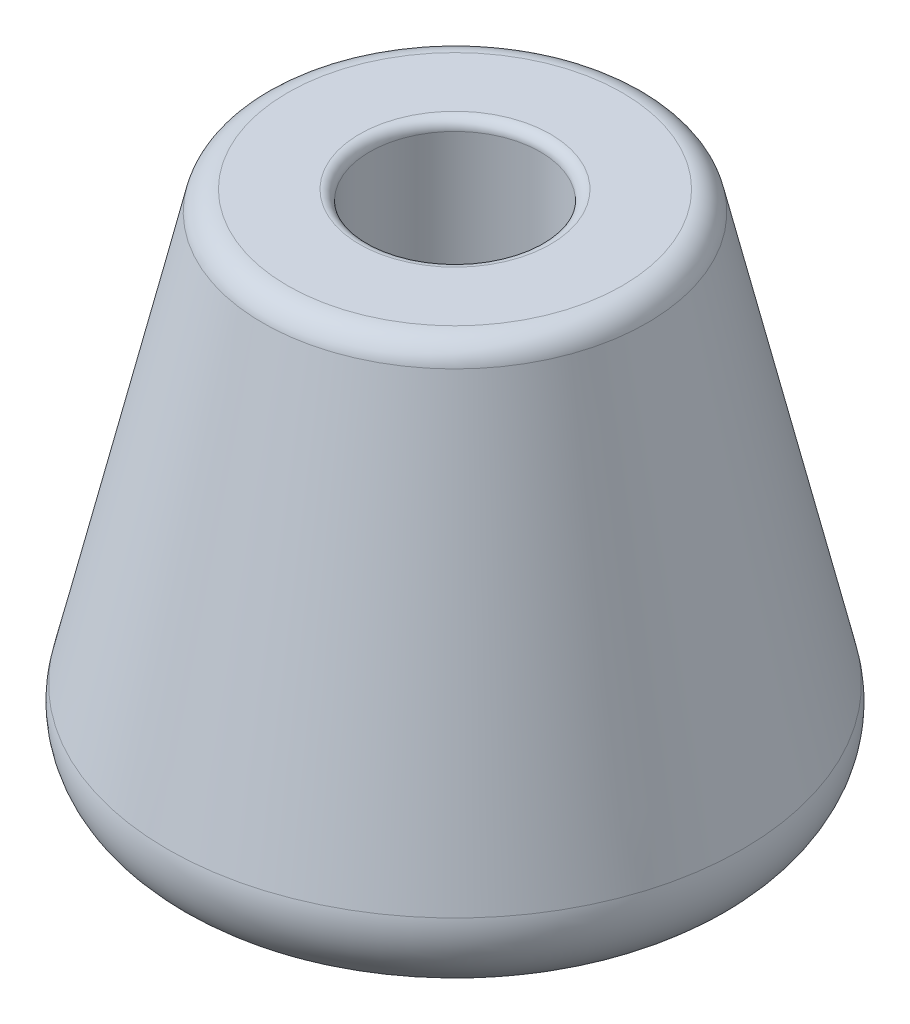
SolidWorks part; units mm, degrees
material "Dostosowane tworzywo sztuczne"
ref_plane "Płaszczyzna przednia" through (0, 0, 0) normal (0, 0, 1) x (1, 0, 0)
ref_plane "Płaszczyzna górna" through (0, 0, 0) normal (0, 1, 0) x (1, 0, 0)
ref_plane "Płaszczyzna prawa" through (0, 0, 0) normal (1, 0, 0) x (0, 0, -1)
sketch "Szkic1" plane through (0, 0, 0) normal (1, 0, 0) x (0, 0, -1)
  line L0 (0, 0) -> (9, 0)
  line L1 (9, 0) -> (5.5, 15)
  line L2 (0, 0) -> (0, 5)
  line L3 (0, 5) -> (0, 15) construction
  line L4 (1.5, 15) -> (2.5, 15) construction
  line L5 (0, 15) -> (2.5, 15) construction
  line L6 (0, 5) -> (2.5, 5)
  line L7 (2.5, 5) -> (2.5, 15)
  line L8 (2.5, 15) -> (5.5, 15)
  point P12 (2.5, 5)
  point P15 (0, 5)
  point P18 (0, 15)
  point P21 (5.5, 15)
  dimension "D1" = 9
revolve "Obrót1" add sketch "Szkic1" angle 360 about L3
fillet "Zaokrąglenie3" radius 0.3 2 edges at (0, 5, -2.5) (0, 15, -2.5)
fillet "Zaokrąglenie4" radius 0.75 1 edges at (0, 15, -5.5)
fillet "Zaokrąglenie5" radius 2 1 edges at (0, 0, -9) type face fillet first side face at (0, 14.4204, -5.6352) second side face at (0, 0, -9)
